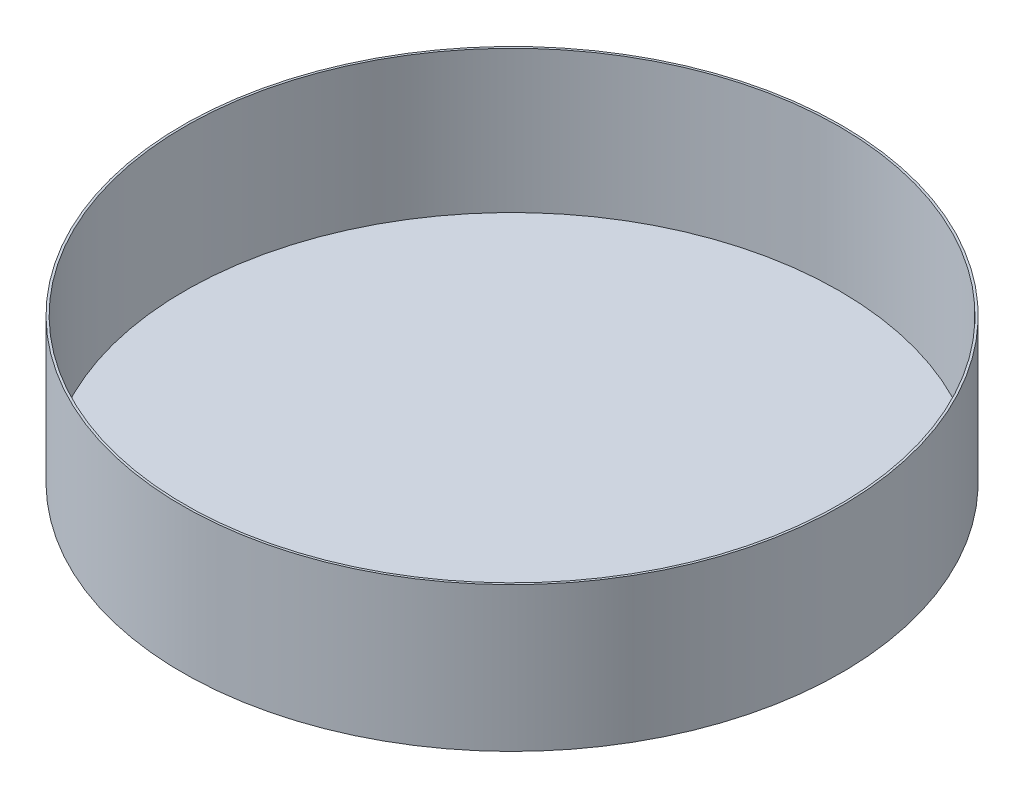
SolidWorks part; units mm, degrees
material "Alumina"
ref_plane "Front Plane" through (0, 0, 0) normal (0, 0, 1) x (1, 0, 0)
ref_plane "Top Plane" through (0, 0, 0) normal (0, 1, 0) x (1, 0, 0)
ref_plane "Right Plane" through (0, 0, 0) normal (1, 0, 0) x (0, 0, -1)
sketch "Sketch1" plane through (0, 0, 0) normal (0, 0, 1) x (1, 0, 0)
  line L0 (0, 0) -> (0, 2000) construction
  line L1 (0, 0) -> (1495.54, 0)
  line L3 (1495.54, 0) -> (1495.54, 650)
  line L5 (0, 0) -> (0, -10) construction
  line L6 (1495.54, 0) -> (1505.54, 0) construction
  line L7 (1505.54, 0) -> (1505.54, -10) construction
  line L8 (0, -10) -> (1505.54, -10)
  line L9 (1505.54, -10) -> (1505.54, 650)
  line L10 (0, 2000) -> (0, 2010) construction
  line L11 (598.217, 2000) -> (598.217, 2010) construction
  line L13 (1046.8785, 1325) -> (1055.2066, 1330.5356) construction
  line L15 (610.2245, 2000) -> (598.217, 2010)
  line L17 (1495.54, 668.065) -> (1505.54, 650)
  line L18 (0, 2010) -> (0, 2000)
  line L19 (0, 0) -> (0, -10)
  line L20 (1505.54, 650) -> (1495.54, 650)
  point P14 (0, 0)
  point P17 (0, 0)
revolve "Revolve1" add sketch "Sketch1" angle 360 about L0
